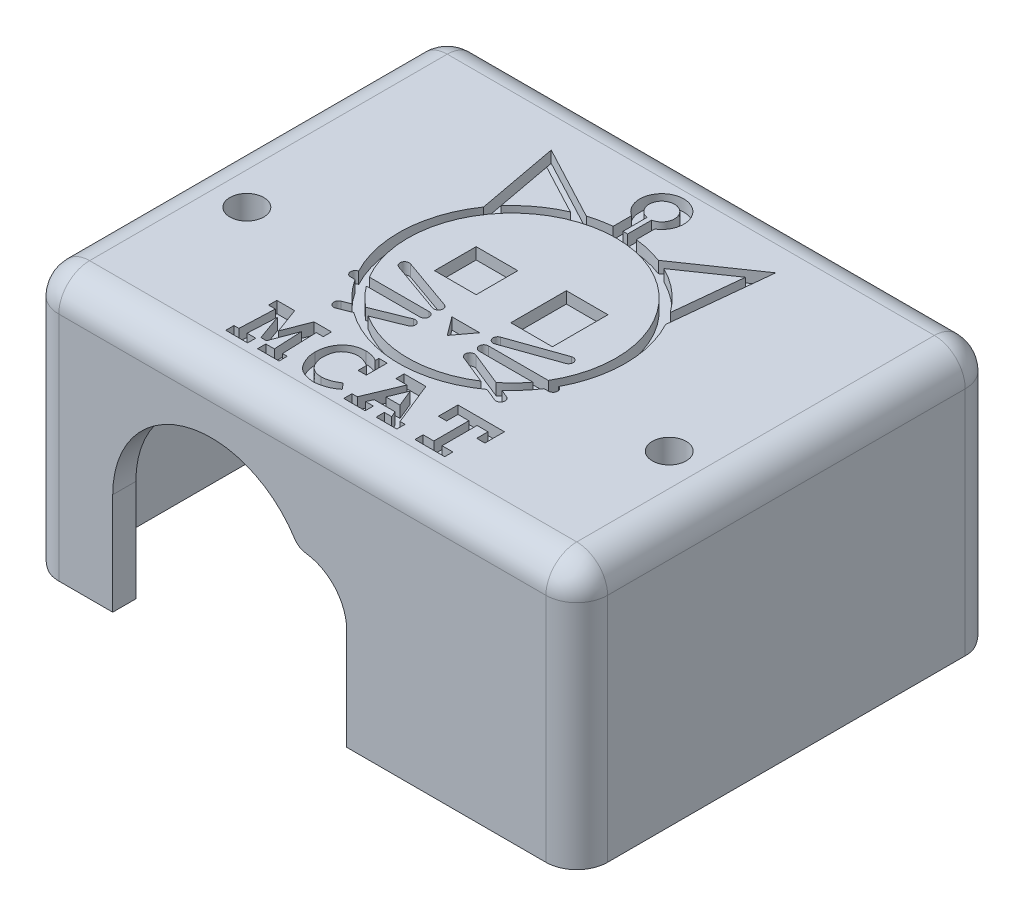
SolidWorks part; units mm, degrees
material "PET"
ref_plane "Front Plane" through (0, 0, 0) normal (0, 0, 1) x (1, 0, 0)
ref_plane "Top Plane" through (0, 0, 0) normal (0, 1, 0) x (1, 0, 0)
ref_plane "Right Plane" through (0, 0, 0) normal (1, 0, 0) x (0, 0, -1)
sketch "Sketch1" plane through (0, 0, 0) normal (0, 1, 0) x (1, 0, 0)
  line L1 (-17.8, 13.6) -> (17.8, 13.6)
  line L2 (-17.8, 13.6) -> (-17.8, -13.6)
  line L3 (-17.8, -13.6) -> (17.8, -13.6)
  line L4 (17.8, 13.6) -> (17.8, -13.6)
  line L5 (-17.8, 13.6) -> (17.8, -13.6) construction
  line L6 (-17.8, -13.6) -> (17.8, 13.6) construction
  point P0 (0, 0)
  dimension "D1" = 35.6
  dimension "D2" = 27.2
extrude "Boss-Extrude1" add sketch "Sketch1" along normal blind 2 contours L3 L4 L1 L2
sketch "Sketch3" plane through (0, 0, 0) normal (0, -1, 0) x (1, 0, 0)
  line L1 (-16.3, 12.1) -> (16.3, 12.1)
  line L2 (-16.3, 12.1) -> (-16.3, -12.1)
  line L3 (-16.3, -12.1) -> (16.3, -12.1)
  line L4 (16.3, 12.1) -> (16.3, -12.1)
  line L5 (-16.3, 12.1) -> (16.3, -12.1) construction
  line L6 (-16.3, -12.1) -> (16.3, 12.1) construction
  line L9 (17.8, 13.6) -> (-17.8, 13.6)
  line L10 (17.8, 13.6) -> (17.8, -13.6)
  line L11 (17.8, -13.6) -> (-17.8, -13.6)
  line L12 (-17.8, 13.6) -> (-17.8, -13.6)
  line L13 (17.8, 13.6) -> (-17.8, -13.6) construction
  line L14 (17.8, -13.6) -> (-17.8, 13.6) construction
  point P0 (0, 0)
  point P6 (0, 0)
  dimension "D1" = 32.6
  dimension "D2" = 24.2
extrude "Boss-Extrude2" add sketch "Sketch3" along normal blind 15
sketch "Sketch5" plane through (0, 0, 13.6) normal (0, 0, 1) x (1, 0, 0)
  line L0 (-12.3, -15) -> (-12.3, -8.4)
  line L1 (17.8, -15) -> (-17.8, -15) construction
  line L2 (2.875, -8.4) -> (2.875, -15)
  line L3 (-17.8, 2) -> (-17.8, -15) construction
  line L4 (-12.3, -15) -> (2.875, -15)
  arc A0 (-12.3, -8.4) -> (-0.2454, -5.4024) centre (-5.9, -8.4) cw
  arc A1 (-0.2454, -5.4024) -> (2.875, -8.4) centre (-0.125, -8.4) cw
  dimension "D3" = 6.6
  dimension "D4" = 6.4
  dimension "D5" = 3
  dimension "D1" = 5.5
  dimension "D2" = 15.175
extrude "Cut-Extrude1" cut sketch "Sketch5" against normal up to next
fillet "Fillet1" radius 1 1 edges at (-0.2454, -5.4024, 12.85)
sketch "Sketch6" plane through (-17.8, 0, 0) normal (-1, 0, 0) x (0, 0, 1)
  line L0 (-8.6, -15) -> (-8.6, -7)
  line L1 (13.6, -15) -> (-13.6, -15) construction
  line L2 (-8.6, -7) -> (-7.35, -7)
  line L3 (-7.35, -7) -> (-7.35, -15)
  line L4 (-8.6, -15) -> (-7.35, -15)
  line L6 (-13.6, 2) -> (-13.6, -15) construction
  dimension "D1" = 1.25
  dimension "D2" = 5
  dimension "D3" = 8
extrude "Cut-Extrude2" cut sketch "Sketch6" against normal up to next
fillet "Fillet2" radius 1 4 edges at (-16.3, -7.5, 12.1) (16.3, -7.5, 12.1) (16.3, -7.5, -12.1) (-16.3, -7.5, -12.1)
sketch "Sketch7" plane through (0, 2, 0) normal (0, 1, 0) x (1, 0, 0)
  line L5 (-17.8, -13.6) -> (17.8, -13.6) construction
  line L6 (-17.8, 13.6) -> (-17.8, -13.6) construction
  line L7 (17.8, 13.6) -> (17.8, -13.6) construction
  circle A0 centre (-13.7, -3.5) radius 1.1
  circle A1 centre (13.7, -3.5) radius 1.1
  dimension "D1" = 10.1
  dimension "D2" = 4.1
  dimension "D3" = 4.1
  dimension "D4" = 2.2
  dimension "D5" = 2.2
extrude "Cut-Extrude3" cut sketch "Sketch7" against normal up to next
fillet "Fillet4" radius 2 8 edges at (0, 2, -13.6) (-17.8, 2, 0) (-17.8, -6.5, 13.6) (0, 2, 13.6) (17.8, 2, 0) (17.8, -6.5, 13.6) (17.8, -6.5, -13.6) (-17.8, -6.5, -13.6)
fillet "Fillet5" radius 1.5 3 edges at (-17.8, -15, 2.125) (-17.8, -15, -10.1) (0, -15, -13.6)
sketch "Sketch8" plane through (0, 2, 0) normal (0, 1, 0) x (1, 0, 0)
  line L0 (0, 11.6) -> (0, -11.6) construction
  line L1 (15.8, 11.6) -> (-15.8, 11.6) construction
  line L2 (-15.8, -11.6) -> (15.8, -11.6) construction
  line L3 (-15.8, 0) -> (15.8, 0) construction
  line L4 (-15.8, 11.6) -> (-15.8, -11.6) construction
  line L5 (15.8, -11.6) -> (15.8, 11.6) construction
  line L6 (-3.375, 1.4375) -> (-3.375, -0.8125) construction
  line L7 (-3.375, -0.8125) -> (-1.125, -0.8125) construction
  line L8 (-1.125, -0.8125) -> (-1.125, 1.4375) construction
  line L9 (-1.125, 1.4375) -> (-3.375, 1.4375) construction
  line L10 (1.125, 1.8125) -> (1.125, -1.1875) construction
  line L11 (1.125, -1.1875) -> (3.375, -1.1875) construction
  line L12 (3.375, -1.1875) -> (3.375, 1.8125) construction
  line L13 (3.375, 1.8125) -> (1.125, 1.8125) construction
  line L14 (-0.75, -2.5) -> (0.75, -2.5) construction
  line L15 (0.75, -2.5) -> (0, -3.5) construction
  line L16 (-0.75, -2.5) -> (0, -3.5) construction
  line L17 (-4.6204, 4.0209) -> (-5.1873, 7.0615) construction
  line L18 (-5.1873, 7.0615) -> (-2.4553, 5.6113) construction
  line L19 (2.7275, 5.4842) -> (5.3385, 7.2823) construction
  line L20 (5.3385, 7.2823) -> (4.957, 3.5978) construction
  line L21 (-0.375, 7.2385) -> (-0.375, 6.1135) construction
  line L22 (0.375, 7.2385) -> (0.375, 6.1135) construction
  line L23 (-1.2469, -3.125) -> (1.3474, -3.125) construction
  line L24 (-1.6, -3.125) -> (-5.35, -3.125) construction
  line L25 (1.6, -3.125) -> (5.35, -3.125) construction
  line L26 (-1.6, -3.875) -> (-4.3811, -5) construction
  line L27 (1.6, -3.875) -> (4.3811, -5) construction
  line L28 (-1.6, -2.375) -> (-4.4284, -1.375) construction
  line L29 (1.6, -2.375) -> (4.4284, -1.375) construction
  line L36 (-5.0308, 3.4938) -> (-5.8689, 7.9893) construction
  line L37 (-5.8689, 7.9893) -> (-1.8297, 5.8453) construction
  line L38 (2.189, 5.7205) -> (5.9474, 8.3088) construction
  line L39 (5.9474, 8.3088) -> (5.3886, 2.9118) construction
  line L40 (0.625, 7.088) -> (0.625, 6.1135) construction
  line L41 (-0.625, 7.088) -> (-0.625, 6.1135) construction
  line L42 (0.125, 7.4217) -> (0.125, 6.1237) construction
  line L43 (-0.125, 7.4217) -> (-0.125, 6.1237) construction
  line L44 (-0.625, 6.1135) -> (-0.625, 6.093)
  line L45 (0.625, 6.1135) -> (0.625, 6.093)
  line L46 (0.125, 7.4217) -> (0.125, 6.1135) construction
  line L47 (-0.125, 7.4217) -> (-0.125, 6.1135) construction
  line L48 (-4.5, 3.375) -> (-5.1873, 7.0615) construction
  line L49 (-5.1873, 7.0615) -> (-1.875, 5.3033) construction
  line L50 (2.25, 5.1554) -> (5.3385, 7.2823) construction
  line L51 (5.3385, 7.2823) -> (4.875, 2.8062) construction
  line L52 (-5.8689, 7.9893) -> (-1.6406, 5.7449) construction
  line L53 (1.9664, 5.5672) -> (5.9474, 8.3088) construction
  line L54 (5.9474, 8.3088) -> (5.3723, 2.7547) construction
  line L55 (-4.9915, 3.2834) -> (-5.8689, 7.9893) construction
  line L56 (-1.5167, -2.1393) -> (-4.3451, -1.1393) construction
  line L57 (-1.6, -2.875) -> (-5.35, -2.875) construction
  line L58 (-1.6937, -3.6432) -> (-4.4748, -4.7682) construction
  line L59 (1.5063, -4.1068) -> (4.2873, -5.2318) construction
  line L60 (1.6, -3.375) -> (5.35, -3.375) construction
  line L61 (1.6833, -2.6107) -> (4.5118, -1.6107) construction
  line L62 (-1.6833, -2.6107) -> (-4.5118, -1.6107) construction
  line L63 (-1.6, -3.375) -> (-5.35, -3.375) construction
  line L64 (-1.5062, -4.1068) -> (-4.2873, -5.2318) construction
  line L65 (1.6938, -3.6432) -> (4.4748, -4.7682) construction
  line L66 (1.6, -2.875) -> (5.35, -2.875) construction
  line L67 (1.5167, -2.1393) -> (4.3451, -1.1393) construction
  line L68 (4.05, -1.425) -> (4.05, 2.175)
  line L69 (-0.75, 8.5056) -> (-0.75, 7.3362)
  line L70 (1.92, -4.05) -> (5.4, -4.05)
  line L71 (-4.05, 1.725) -> (-4.05, -0.975)
  line L72 (-2.02, -3.1328) -> (-5.4141, -1.9328)
  line L73 (1.92, -3.45) -> (5.8017, -3.45)
  line L74 (1.35, -1.425) -> (4.05, -1.425)
  line L75 (7.1369, 9.9705) -> (6.4663, 3.4942)
  line L76 (-1.92, -4.05) -> (-5.4, -4.05)
  line L77 (-1.92, -4.65) -> (-5.2573, -6) construction
  line L78 (-0.9, -3) -> (0, -4.2)
  line L79 (-5.5445, 4.825) -> (-6.2248, 8.4738)
  line L80 (0.75, 7.3362) -> (0.75, 7.3116)
  line L81 (-1.8075, -4.9281) -> (-3.6544, -5.6752)
  line L82 (6.4062, 8.7388) -> (5.9484, 4.3174)
  line L83 (-1.4962, -3.75) -> (1.6169, -3.75) construction
  line L84 (-1.35, 1.725) -> (-4.05, 1.725)
  line L85 (-6.2248, 8.4738) -> (-2.9464, 6.7336)
  line L86 (-0.75, 7.3362) -> (-0.75, 7.3116)
  line L87 (1.92, -3.75) -> (6.42, -3.75) construction
  line L88 (0.75, 8.5056) -> (0.75, 7.3362)
  line L89 (-1.92, -3.45) -> (-5.8017, -3.45)
  line L90 (-1.92, -2.85) -> (-5.3141, -1.65) construction
  line L91 (4.05, 2.175) -> (1.35, 2.175)
  line L92 (0.15, 8.906) -> (0.15, 7.3485)
  line L93 (1.8075, -4.9281) -> (3.6544, -5.6752)
  line L94 (-0.45, 8.6862) -> (-0.45, 7.3362) construction
  line L95 (-4.05, -0.975) -> (-1.35, -0.975)
  line L96 (-7.0427, 9.5872) -> (-2.1956, 7.0144)
  line L97 (2.02, -3.1328) -> (5.4141, -1.9328)
  line L98 (0.9, -3) -> (0, -4.2)
  line L99 (-0.9, -3) -> (0.9, -3)
  line L100 (1.82, -2.5672) -> (5.2141, -1.3672)
  line L101 (1.35, 2.175) -> (1.35, -1.425)
  line L102 (-0.15, 8.906) -> (-0.15, 7.3485)
  line L103 (0.45, 8.6862) -> (0.45, 7.3362) construction
  line L104 (3.273, 6.5811) -> (6.4062, 8.7388)
  line L105 (-6.0369, 4.1926) -> (-7.0427, 9.5872)
  line L106 (2.0325, -4.3719) -> (4.2295, -5.2606)
  line L107 (-1.92, -3.75) -> (-6.42, -3.75) construction
  line L108 (-1.35, -0.975) -> (-1.35, 1.725)
  line L109 (2.6268, 6.8646) -> (7.1369, 9.9705)
  line L110 (-1.82, -2.5672) -> (-5.2141, -1.3672)
  line L111 (1.92, -4.65) -> (5.2573, -6) construction
  line L112 (-2.0325, -4.3719) -> (-4.2295, -5.2606)
  line L113 (1.92, -2.85) -> (5.3141, -1.65) construction
  line L114 (-4.8586, -5.5151) -> (-5.3698, -5.7219)
  line L115 (-4.3217, -5.9452) -> (-5.1448, -6.2781)
  line L116 (-6.1335, -4.05) -> (-6.42, -4.05)
  line L117 (4.8586, -5.5151) -> (5.3698, -5.7219)
  line L118 (4.3217, -5.9452) -> (5.1448, -6.2781)
  line L119 (6.1335, -4.05) -> (6.42, -4.05)
  circle A0 centre (0, 0) radius 5.625 construction
  arc A1 (0.375, 7.2385) -> (-0.375, 7.2385) centre (0, 8.0977) ccw construction
  arc A2 (-5.0308, 3.4938) -> (5.3886, 2.9118) centre (0, 0) ccw construction
  arc A3 (0.625, 7.088) -> (-0.625, 7.088) centre (0, 8.0977) ccw construction
  arc A4 (0.125, 7.4217) -> (-0.125, 7.4217) centre (0, 8.0977) ccw construction
  circle A5 centre (0, 0) radius 6.125 construction
  arc A6 (-2.4553, 5.6113) -> (-4.6204, 4.0209) centre (0, 0) ccw construction
  arc A7 (2.189, 5.7205) -> (0.625, 6.093) centre (0, 0) ccw construction
  arc A8 (4.957, 3.5978) -> (2.7275, 5.4842) centre (0, 0) ccw construction
  arc A9 (-0.625, 6.093) -> (-1.8297, 5.8453) centre (0, 0) ccw construction
  arc A10 (0.125, 6.1237) -> (-0.125, 6.1237) centre (0, 0) ccw construction
  arc A11 (-1.5167, -2.1393) -> (-1.6833, -2.6107) centre (-1.6, -2.375) cw construction
  arc A12 (-4.3451, -1.1393) -> (-4.5118, -1.6107) centre (-4.4284, -1.375) ccw construction
  arc A13 (-1.6, -2.875) -> (-1.6, -3.375) centre (-1.6, -3.125) cw construction
  arc A14 (-5.35, -2.875) -> (-5.35, -3.375) centre (-5.35, -3.125) ccw construction
  arc A15 (-1.6937, -3.6432) -> (-1.5062, -4.1068) centre (-1.6, -3.875) cw construction
  arc A16 (-4.4748, -4.7682) -> (-4.2873, -5.2318) centre (-4.3811, -5) ccw construction
  arc A17 (1.5063, -4.1068) -> (1.6938, -3.6432) centre (1.6, -3.875) cw construction
  arc A18 (4.2873, -5.2318) -> (4.4748, -4.7682) centre (4.3811, -5) ccw construction
  arc A19 (1.6, -3.375) -> (1.6, -2.875) centre (1.6, -3.125) cw construction
  arc A20 (5.35, -3.375) -> (5.35, -2.875) centre (5.35, -3.125) ccw construction
  arc A21 (1.6833, -2.6107) -> (1.5167, -2.1393) centre (1.6, -2.375) cw construction
  arc A22 (4.5118, -1.6107) -> (4.3451, -1.1393) centre (4.4284, -1.375) ccw construction
  arc A23 (-1.92, -3.45) -> (-1.92, -4.05) centre (-1.92, -3.75) cw
  arc A24 (-2.9464, 6.7336) -> (-5.5445, 4.825) centre (0, 0) ccw
  arc A25 (0.15, 8.906) -> (-0.15, 8.906) centre (0, 9.7173) ccw
  arc A26 (-0.75, 7.3116) -> (-2.1956, 7.0144) centre (0, 0) ccw
  arc A27 (6.42, -4.05) -> (6.4861, -3.4574) centre (6.42, -3.75) ccw
  arc A28 (0.75, 8.5056) -> (-0.75, 8.5056) centre (0, 9.7173) ccw
  arc A29 (0.15, 7.3485) -> (-0.15, 7.3485) centre (0, 0) ccw
  arc A30 (-6.4861, -3.4574) -> (-6.42, -4.05) centre (-6.42, -3.75) ccw
  arc A31 (-5.3698, -5.7219) -> (-5.1448, -6.2781) centre (-5.2573, -6) ccw
  arc A32 (-2.0325, -4.3719) -> (-1.8075, -4.9281) centre (-1.92, -4.65) cw
  arc A33 (0.45, 8.6862) -> (-0.45, 8.6862) centre (0, 9.7173) ccw construction
  arc A34 (5.9484, 4.3174) -> (3.273, 6.5811) centre (0, 0) ccw
  arc A35 (2.02, -3.1328) -> (1.82, -2.5672) centre (1.92, -2.85) cw
  arc A36 (-6.0369, 4.1926) -> (-6.4861, -3.4574) centre (0, 0) ccw
  arc A37 (-5.4, -4.05) -> (-4.2295, -5.2606) centre (0, 0) ccw
  arc A38 (1.92, -4.05) -> (1.92, -3.45) centre (1.92, -3.75) cw
  arc A39 (1.8075, -4.9281) -> (2.0325, -4.3719) centre (1.92, -4.65) cw
  arc A40 (-1.82, -2.5672) -> (-2.02, -3.1328) centre (-1.92, -2.85) cw
  arc A41 (2.6268, 6.8646) -> (0.75, 7.3116) centre (0, 0) ccw
  arc A42 (-5.2141, -1.3672) -> (-5.4141, -1.9328) centre (-5.3141, -1.65) ccw
  arc A43 (5.4141, -1.9328) -> (5.2141, -1.3672) centre (5.3141, -1.65) ccw
  arc A44 (5.1448, -6.2781) -> (5.3698, -5.7219) centre (5.2573, -6) ccw
  arc A45 (-6.1335, -4.05) -> (-4.8586, -5.5151) centre (0, 0) ccw
  arc A46 (6.4861, -3.4574) -> (6.4663, 3.4942) centre (0, 0) ccw
  arc A47 (5.8017, -3.45) -> (-5.8017, -3.45) centre (0, 0) ccw
  arc A48 (4.2295, -5.2606) -> (5.4, -4.05) centre (0, 0) ccw
  arc A49 (4.8586, -5.5151) -> (6.1335, -4.05) centre (0, 0) ccw
  arc A50 (-3.6544, -5.6752) -> (3.6544, -5.6752) centre (0, 0) ccw
  arc A51 (-4.3217, -5.9452) -> (4.3217, -5.9452) centre (0, 0) ccw
  point P40 (0, -5.625)
  point P129 (0, -6.75)
  dimension "D1" = 11.25
  dimension "D2" = 1.875
  dimension "D3" = 1.125
  dimension "D4" = 0.75
  dimension "D5" = 1.25
  dimension "D6" = 1.5
  dimension "D7" = 1.25
  dimension "D8" = 2.125
  dimension "D9" = 1.3125
  dimension "D10" = 1.6875
  dimension "D11" = 2.25
  dimension "D12" = 2.25
  dimension "D13" = 2.25
  dimension "D14" = 3
  dimension "D15" = 2.25
  dimension "D16" = 4.957
  dimension "D17" = 2.7275
  dimension "D18" = 4.6204
  dimension "D19" = 2.4553
  dimension "D20" = 3.1703
  dimension "D21" = 3.7042
  dimension "D22" = 3.093
  dimension "D23" = 3.093
  dimension "D24" = 3.75
  dimension "D25" = 3.75
  dimension "D26" = 2.5
  dimension "D27" = 1.6
  dimension "D28" = 1.125
  dimension "D29" = 1.125
  dimension "D30" = 3
  dimension "D31" = 3
  dimension "D32" = 0.75
  dimension "D33" = 0.75
  dimension "D34" = 0.75
  dimension "D35" = 1
  dimension "D36" = 1
  dimension "D37" = 3
  dimension "D38" = 3
  dimension "D39" = 1.6
  dimension "D40" = 0.5
  dimension "D41" = 0.5
  dimension "D42" = 0.5
  dimension "D43" = 0.25
  dimension "D44" = 0.25
  dimension "D45" = 0.25
  dimension "D46" = 0.25
extrude "Cut-Extrude4" cut sketch "Sketch8" along direction (0, 1, 0) on the side against the normal blind 0.75 contours L115 A51 L118 A44 L117 A49 L119 A27 A46 L75 L109 A41 L80 L88 A28 L69 L86 A26 L96 L105 A36 A30 L116 A45 L114 A31 L82 A34 L104 L92 A29 L102 A25 L85 A24 L79 A50 L81 A32 L112 A37 L76 A23 L89 A47 L73 A38 | L91 L101 L74 L68 | L95 L108 L84 L71 | L97 A43 L100 A35 | L110 A42 L72 A40 | L99 L78 L98
sketch "Sketch9" plane through (0, 2, 0) normal (0, 1, 0) x (1, 0, 0)
  line L0 (-10.8, -11.1) -> (10.8, -11.1) construction
  line L1 (-15.8, -11.6) -> (15.8, -11.6) construction
  line L2 (-15.8, 11.6) -> (-15.8, -11.6) construction
  line L3 (15.8, -11.6) -> (15.8, 11.6) construction
  text T0 "MCAT" font "Courier Std" height in points 13
  dimension "D1" = 0.5
  dimension "D2" = 5
  dimension "D3" = 5
extrude "Cut-Extrude5" cut sketch "Sketch9" against normal blind 0.75
